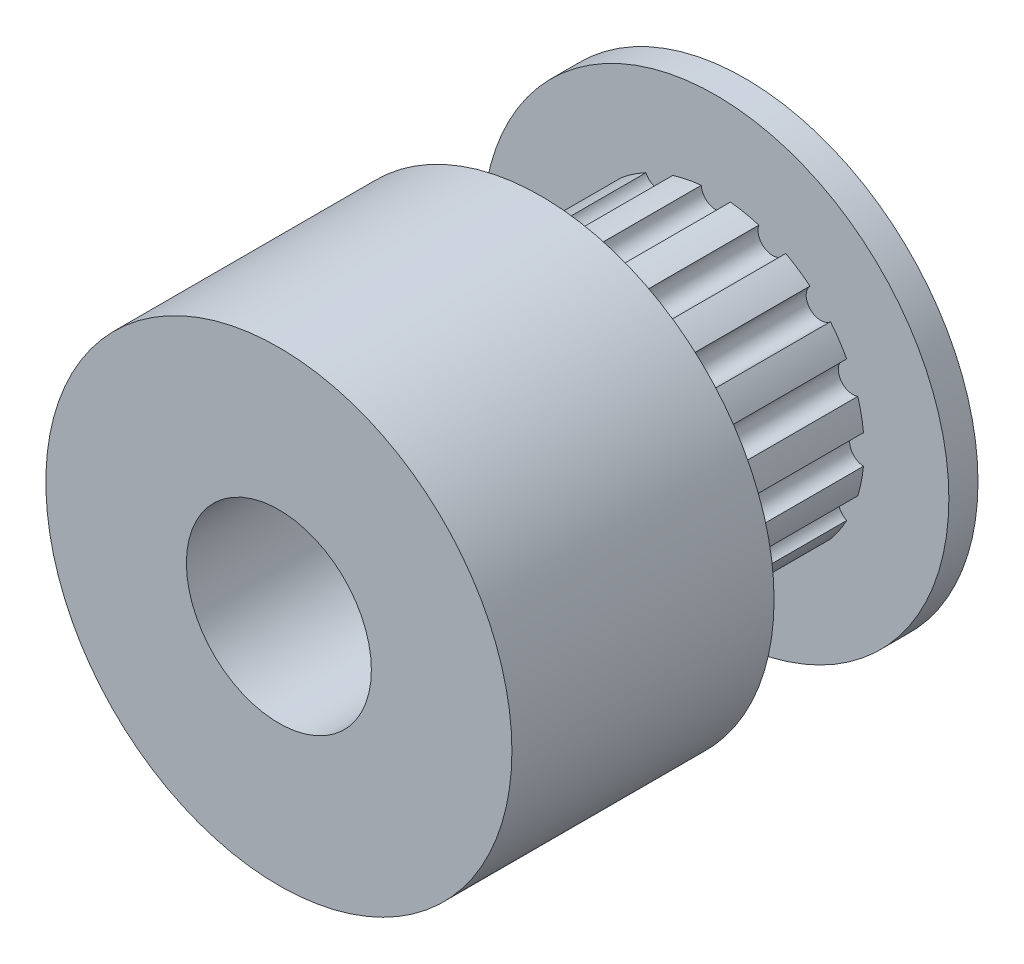
SolidWorks part; units mm, degrees
material "1060 Alloy"
ref_plane "Front Plane" through (0, 0, 0) normal (0, 0, 1) x (1, 0, 0)
ref_plane "Top Plane" through (0, 0, 0) normal (0, 1, 0) x (1, 0, 0)
ref_plane "Right Plane" through (0, 0, 0) normal (1, 0, 0) x (0, 0, -1)
sketch "Sketch1" plane through (0, 0, 0) normal (0, 0, 1) x (1, 0, 0)
  circle A0 centre (0, 0) radius 8
  circle A1 centre (0, 0) radius 3.175
  dimension "D1" = 16
  dimension "D2" = 6.35
extrude "Boss-Extrude1" add sketch "Sketch1" along normal blind 1 contours A0 A1 | A1 | A0 | A1 region at (-7.7737, 0, 0) region at (0, 0, 0)
sketch "Sketch2" plane through (0, 0, 1) normal (0, 0, 1) x (1, 0, 0)
  arc A0 (-0.4994, 5.0684) -> (-1.4782, 4.8737) centre (0, 0) ccw
  arc A1 (-0.4994, 5.0684) -> (0.4994, 5.0684) centre (0, 5.093) ccw
  arc A2 (1.4782, 4.8737) -> (2.401, 4.4915) centre (1.949, 4.7053) ccw
  arc A3 (3.2308, 3.937) -> (3.937, 3.2308) centre (3.6013, 3.6013) ccw
  arc A4 (4.4915, 2.401) -> (4.8737, 1.4782) centre (4.7053, 1.949) ccw
  arc A5 (5.0684, 0.4994) -> (5.0684, -0.4994) centre (5.093, 0) ccw
  arc A6 (4.8737, -1.4782) -> (4.4915, -2.401) centre (4.7053, -1.949) ccw
  arc A7 (3.937, -3.2308) -> (3.2308, -3.937) centre (3.6013, -3.6013) ccw
  arc A8 (2.401, -4.4915) -> (1.4782, -4.8737) centre (1.949, -4.7053) ccw
  arc A9 (0.4994, -5.0684) -> (-0.4994, -5.0684) centre (0, -5.093) ccw
  arc A10 (-1.4782, -4.8737) -> (-2.401, -4.4915) centre (-1.949, -4.7053) ccw
  arc A11 (-3.2308, -3.937) -> (-3.937, -3.2308) centre (-3.6013, -3.6013) ccw
  arc A12 (-4.4915, -2.401) -> (-4.8737, -1.4782) centre (-4.7053, -1.949) ccw
  arc A13 (-5.0684, -0.4994) -> (-5.0684, 0.4994) centre (-5.093, 0) ccw
  arc A14 (-4.8737, 1.4782) -> (-4.4915, 2.401) centre (-4.7053, 1.949) ccw
  arc A15 (-3.937, 3.2308) -> (-3.2308, 3.937) centre (-3.6013, 3.6013) ccw
  arc A16 (-2.401, 4.4915) -> (-1.4782, 4.8737) centre (-1.949, 4.7053) ccw
  arc A17 (-2.401, 4.4915) -> (-3.2308, 3.937) centre (0, 0) ccw
  arc A18 (1.4782, 4.8737) -> (0.4994, 5.0684) centre (0, 0) ccw
  arc A19 (3.2308, 3.937) -> (2.401, 4.4915) centre (0, 0) ccw
  arc A20 (4.4915, 2.401) -> (3.937, 3.2308) centre (0, 0) ccw
  arc A21 (5.0684, 0.4994) -> (4.8737, 1.4782) centre (0, 0) ccw
  arc A22 (4.8737, -1.4782) -> (5.0684, -0.4994) centre (0, 0) ccw
  arc A23 (3.937, -3.2308) -> (4.4915, -2.401) centre (0, 0) ccw
  arc A24 (2.401, -4.4915) -> (3.2308, -3.937) centre (0, 0) ccw
  arc A25 (0.4994, -5.0684) -> (1.4782, -4.8737) centre (0, 0) ccw
  arc A26 (-1.4782, -4.8737) -> (-0.4994, -5.0684) centre (0, 0) ccw
  arc A27 (-3.2308, -3.937) -> (-2.401, -4.4915) centre (0, 0) ccw
  arc A28 (-4.4915, -2.401) -> (-3.937, -3.2308) centre (0, 0) ccw
  arc A29 (-5.0684, -0.4994) -> (-4.8737, -1.4782) centre (0, 0) ccw
  arc A30 (-4.8737, 1.4782) -> (-5.0684, 0.4994) centre (0, 0) ccw
  arc A31 (-3.937, 3.2308) -> (-4.4915, 2.401) centre (0, 0) ccw
  point P52 (0, 0)
  dimension "D1" = 10.1859
  dimension "D2" = 1
  dimension "D3" = 16
extrude "Boss-Extrude2" add sketch "Sketch2" along normal blind 6
sketch "Sketch3" plane through (0, 0, 7) normal (0, 0, 1) x (1, 0, 0)
  circle A0 centre (0, 0) radius 8
  dimension "D1" = 16
extrude "Boss-Extrude3" add sketch "Sketch3" along normal blind 9
extrude "Cut-Extrude1" cut sketch "Sketch1<3>" along normal through all contours A1 region at (0, 0, 0)
sketch "Sketch1<3>" plane through (0, 0, 0) normal (0, 0, 1) x (1, 0, 0) same geometry as "Sketch1"
